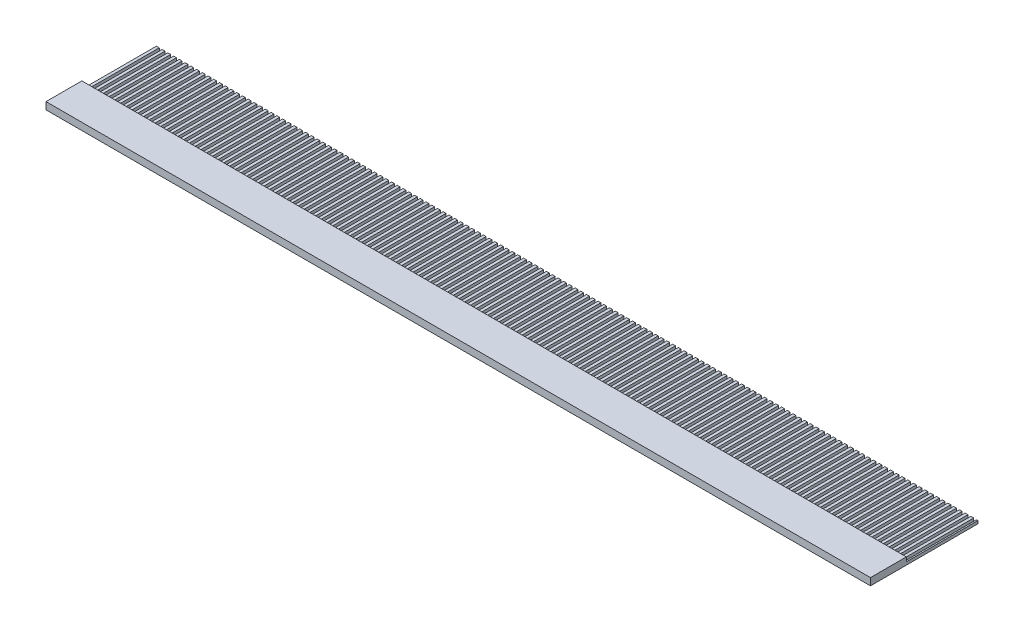
SolidWorks part; units mm, degrees
ref_plane "Front Plane" through (0, 0, 0) normal (0, 0, 1) x (1, 0, 0)
ref_plane "Top Plane" through (0, 0, 0) normal (0, 1, 0) x (1, 0, 0)
ref_plane "Right Plane" through (0, 0, 0) normal (1, 0, 0) x (0, 0, -1)
sketch "Sketch1" plane through (0, 0, 0) normal (0, 1, 0) x (1, 0, 0)
  line L1 (0, 0) -> (115, 0)
  line L2 (0, 0) -> (0, 15)
  line L3 (0, 15) -> (115, 15)
  line L4 (115, 0) -> (115, 15)
extrude "Boss-Extrude1" add sketch "Sketch1" along normal blind 0.5
sketch "Sketch2" plane through (0, 0.5, 0) normal (0, 1, 0) x (1, 0, 0)
  line L0 (115, 0) -> (115, 15) construction
  line L1 (0, 15) -> (115, 15)
  line L2 (0, 15) -> (0, 5)
  line L3 (0, 5) -> (115, 5)
  line L4 (115, 15) -> (115, 5)
extrude "Cut-Extrude1" cut sketch "Sketch2" against normal blind 0.1
sketch "Sketch3" plane through (0, 0.4, 0) normal (0, 1, 0) x (1, 0, 0)
  line L0 (0, 5) -> (115, 5) construction
  line L1 (0, 15) -> (0.4, 15)
  line L2 (0, 15) -> (0, 5)
  line L3 (0, 5) -> (0.4, 5)
  line L4 (0.4, 15) -> (0.4, 5)
extrude "Cut-Extrude2" cut sketch "Sketch3" against normal blind 0.4
pattern_linear "LPattern3" count 150 spacing 0.8 along (1, 0, 0) of "Cut-Extrude2"
sketch "Sketch4" plane through (0, 0, 0) normal (0, -1, 0) x (1, 0, 0)
  line L0 (0, -5) -> (0, 0) construction
  line L1 (0, -5) -> (115, -5)
  line L2 (0, -5) -> (0, 0)
  line L3 (0, 0) -> (115, 0)
  line L4 (115, -5) -> (115, 0)
  line L5 (0, -5) -> (0.4, -5) construction
extrude "Boss-Extrude2" add sketch "Sketch4" against normal blind 1
